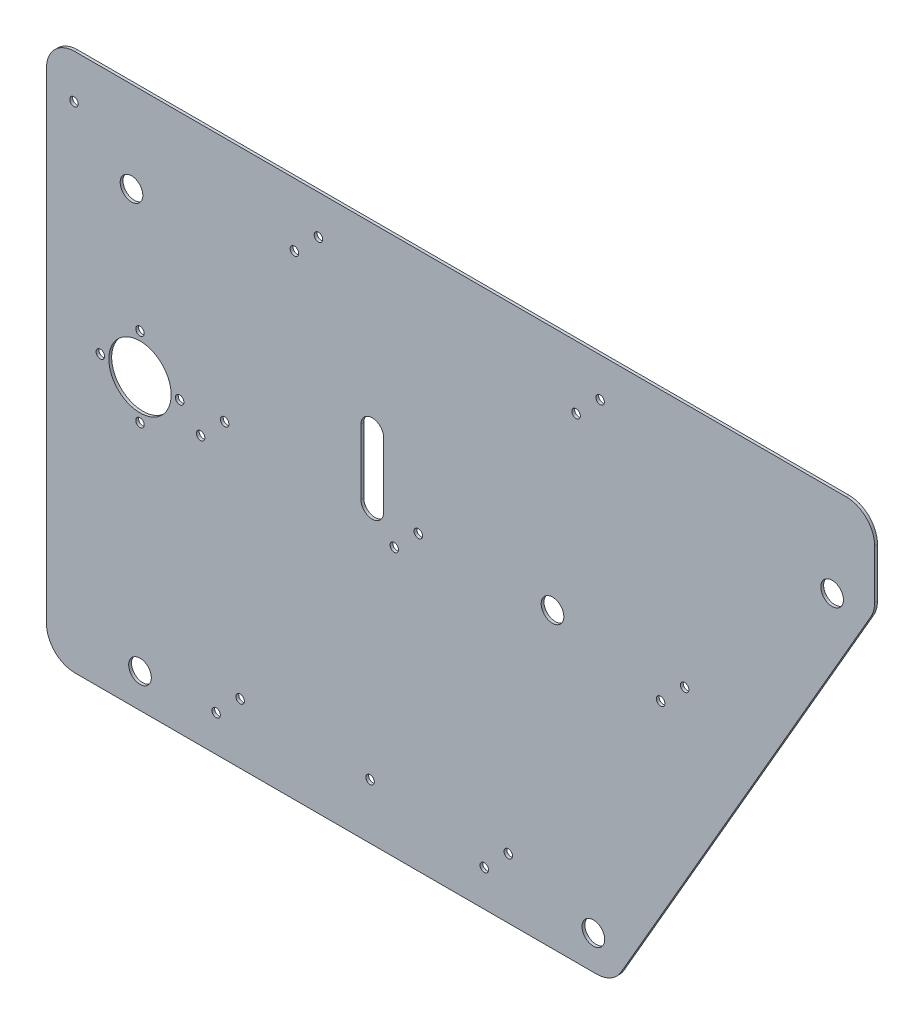
SolidWorks part; units mm, degrees
ref_plane "Front Plane" through (0, 0, 0) normal (0, 0, 1) x (1, 0, 0)
ref_plane "Top Plane" through (0, 0, 0) normal (0, 1, 0) x (1, 0, 0)
ref_plane "Right Plane" through (0, 0, 0) normal (1, 0, 0) x (0, 0, -1)
sketch "Sketch1" plane through (0, 0, 0) normal (0, 0, 1) x (1, 0, 0)
  line L0 (100, 80) -> (192.376, 80)
  line L1 (-100, -80) -> (100, -80)
  line L2 (-100, -80) -> (-100, 80)
  line L3 (-100, 80) -> (100, 80)
  line L4 (100, -80) -> (100, 80)
  line L5 (-100, -80) -> (100, 80) construction
  line L6 (-100, 80) -> (100, -80) construction
  line L7 (192.376, 80) -> (100, -80)
  line L8 (100, 80) -> (100, -80)
  line L10 (-100, 80) -> (192.376, 80)
  line L11 (-100, 80) -> (-100, 110)
  line L12 (-100, 110) -> (192.376, 110)
  line L13 (192.376, 80) -> (192.376, 110)
  point P0 (0, 0)
  dimension "D1" = 160
  dimension "D2" = 200
  dimension "D3" = 30
  dimension "D4" = 30
extrude "Boss-Extrude1" add sketch "Sketch1" along normal blind 1 contours L1 L4 L3 L2 | L7 L0 L4 | L11 L10 L13 L12 region at (0, 0, 0) region at (130.792, 26.6667, 0)
fillet "Fillet1" radius 10 5 edges at (100, -80, 0.5) (-100, -80, 0.5) (192.376, 110, 0.5) (192.376, 80, 0.5) (-100, 110, 0.5)
sketch "Sketch2" plane through (0, 0, 1) normal (0, 0, 1) x (1, 0, 0)
  line L0 (-90, -80) -> (94.2265, -80) construction
  line L1 (191.0363, 77.6795) -> (102.8868, -75) construction
  line L2 (0, -0.55) -> (0, 0.55) construction
  line L3 (-100, -70) -> (-100, 100) construction
  line L4 (15, 23.5) -> (15, 46.5) construction
  line L5 (11, 23.5) -> (11, 46.5)
  line L6 (19, 23.5) -> (19, 46.5)
  line L7 (-90, 110) -> (182.376, 110) construction
  line L8 (-100, -70) -> (-100, 100) construction
  circle A0 centre (93.0718, -68) radius 4
  circle A1 centre (177.3649, 78) radius 4
  circle A2 centre (-67, 22) radius 11
  circle A3 centre (-67, -68) radius 4
  circle A4 centre (-53, 22) radius 1.5
  circle A5 centre (-67, 36) radius 1.5
  circle A6 centre (-81, 22) radius 1.5
  circle A7 centre (-67, 8) radius 1.5
  arc A8 (11, 23.5) -> (19, 23.5) centre (15, 23.5) ccw
  arc A9 (19, 46.5) -> (11, 46.5) centre (15, 46.5) ccw
  circle A10 centre (-70, 78) radius 4
  circle A11 centre (54.5495, -67.2426) radius 1.5
  circle A12 centre (63.0348, -58.7574) radius 1.5
  circle A13 centre (14.2259, -60.5) radius 1.5
  circle A14 centre (-40.1271, -67.2426) radius 1.5
  circle A15 centre (-31.6419, -58.7574) radius 1.5
  circle A16 centre (-90.2956, 94.5) radius 1.5
  circle A17 centre (-12.4828, 87.7574) radius 1.5
  circle A18 centre (-3.9975, 96.2426) radius 1.5
  circle A19 centre (86.9654, 87.7574) radius 1.5
  circle A20 centre (95.4507, 96.2426) radius 1.5
  circle A21 centre (22.7626, 14.7574) radius 1.5
  circle A22 centre (31.2479, 23.2426) radius 1.5
  circle A23 centre (-45.6014, 14.7574) radius 1.5
  circle A24 centre (-37.1161, 23.2426) radius 1.5
  circle A25 centre (116.8113, 14.7574) radius 1.5
  circle A26 centre (125.2966, 23.2426) radius 1.5
  circle A27 centre (78.6382, 23.5) radius 4
  point P24 (15, 35)
  point P33 (0, 0)
  point P83 (79.8055, 52.1193)
  point P85 (79.9263, 28.5)
  point P90 (78.6382, 23.2426)
  point P91 (0, 0)
  dimension "D3" = 8
  dimension "D4" = 8
  dimension "D9" = 22
  dimension "D10" = 8
  dimension "D12" = 3
  dimension "D13" = 3
  dimension "D14" = 3
  dimension "D15" = 3
  dimension "D16" = 14
  dimension "D20" = 4
  dimension "D22" = 8
  dimension "D25" = 3
  dimension "D26" = 3
  dimension "D29" = 8
  dimension "D1" = 12
  dimension "D2" = 12
  dimension "D5" = 32
  dimension "D6" = 12
  dimension "D7" = 88
  dimension "D8" = 33
  dimension "D11" = 12
  dimension "D17" = 14
  dimension "D18" = 14
  dimension "D19" = 14
  dimension "D21" = 23
  dimension "D23" = 75
  dimension "D24" = 32
  dimension "D27" = 15
  dimension "D28" = 30
extrude "Cut-Extrude1" cut sketch "Sketch2" against normal blind 3
